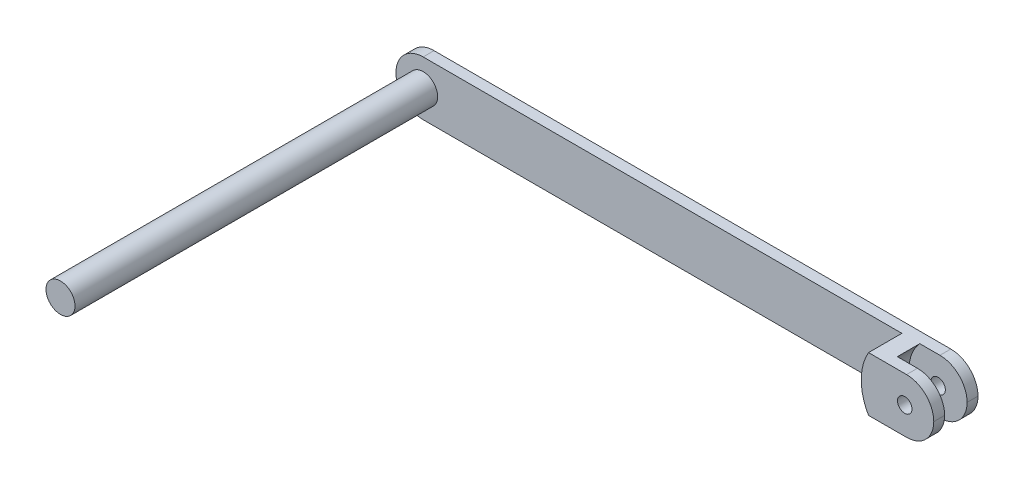
SolidWorks part; units mm, degrees
material "PBT General Purpose"
ref_plane "Front Plane" through (0, 0, 0) normal (0, 0, 1) x (1, 0, 0)
ref_plane "Top Plane" through (0, 0, 0) normal (0, 1, 0) x (1, 0, 0)
ref_plane "Right Plane" through (0, 0, 0) normal (1, 0, 0) x (0, 0, -1)
sketch "Sketch1" plane through (0, 0, 0) normal (0, 0, 1) x (1, 0, 0)
  line L0 (0, 7.5) -> (150, 7.5)
  line L6 (0, -7.5) -> (150, -7.5)
  line L7 (150, 7.5) -> (150, -7.5)
  arc A2 (0, 7.5) -> (0, -7.5) centre (0, 0) ccw
  dimension "D1" = 15
  dimension "D2" = 150
extrude "Boss-Extrude1" add sketch "Sketch1" along normal blind 3
sketch "Sketch2" plane through (0, 0, 3) normal (0, 0, 1) x (1, 0, 0)
  circle A0 centre (0, 0) radius 4
extrude "Boss-Extrude2" add sketch "Sketch2" along normal blind 8
sketch "Sketch3" plane through (0, 0, 11) normal (0, 0, 1) x (1, 0, 0)
  circle A0 centre (0, 0) radius 4 construction
  circle A1 centre (0, 0) radius 4
extrude "Boss-Extrude3" add sketch "Sketch3" along normal blind 92
sketch "Sketch7" plane through (0, 0, 3) normal (0, 0, 1) x (1, 0, 0)
  line L0 (150, 7.5) -> (0, 7.5) construction
  line L1 (150, -7.5) -> (150, 7.5) construction
  line L2 (136.9533, 7.5) -> (132.0096, 7.5)
  line L3 (0, -7.5) -> (150, -7.5) construction
  line L4 (132.0096, -7.5) -> (136.9533, -7.5)
  arc A0 (132.0096, 7.5) -> (132.0096, -7.5) centre (145, 0) ccw
  arc A1 (136.9533, 7.5) -> (136.9533, -7.5) centre (145, 0) ccw
  dimension "D1" = 30
  dimension "D2" = 22
  dimension "D3" = 7.5
  dimension "D4" = 5
extrude "Boss-Extrude6" add sketch "Sketch7" along normal blind 9.2
sketch "Sketch8" plane through (150, 0, 0) normal (1, 0, 0) x (0, 0, -1)
  line L0 (-12.2, 7.5) -> (-3, 7.5) construction
  line L1 (-12.2, -7.5) -> (-9.2, -7.5)
  line L2 (-12.2, -7.5) -> (-12.2, 7.5)
  line L3 (-12.2, 7.5) -> (-9.2, 7.5)
  line L4 (-9.2, -7.5) -> (-9.2, 7.5)
  dimension "D1" = 3
extrude "Boss-Extrude7" add sketch "Sketch8" against normal up to surface (17.9904 mm away) up to face at (131.0048, 0, 7.6)
sketch "Sketch9" plane through (0, 0, 12.2) normal (0, 0, 1) x (1, 0, 0)
  line L0 (150, 7.5) -> (132.0096, 7.5) construction
  line L1 (150, 7.5) -> (150, -7.5) construction
  circle A0 centre (142, 0) radius 2
  dimension "D1" = 4
  dimension "D2" = 7.5
  dimension "D3" = 8
extrude "Cut-Extrude2" cut sketch "Sketch9" against normal through all
fillet "Fillet2" radius 7.5 4 edges at (150, -7.5, 1.5) (150, -7.5, 10.7) (150, 7.5, 1.5) (150, 7.5, 10.7)
